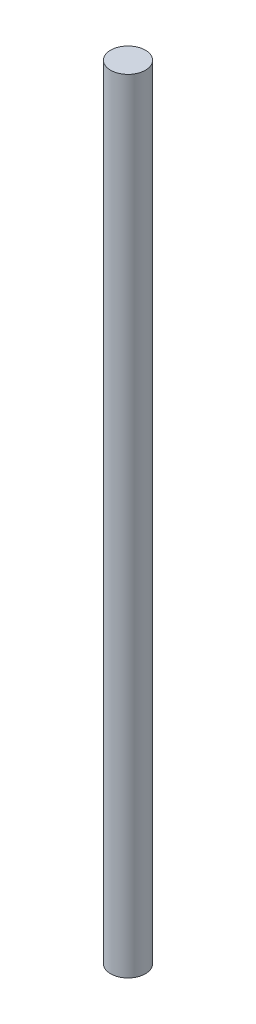
SolidWorks part; units mm, degrees
ref_plane "Front Plane" through (0, 0, 0) normal (0, 0, 1) x (1, 0, 0)
ref_plane "Top Plane" through (0, 0, 0) normal (0, 1, 0) x (1, 0, 0)
ref_plane "Right Plane" through (0, 0, 0) normal (1, 0, 0) x (0, 0, -1)
sketch "Sketch1" plane through (0, 0, 0) normal (0, 1, 0) x (1, 0, 0)
  circle A0 centre (0, 0) radius 4
  dimension "D1" = 8
extrude "Boss-Extrude1" add sketch "Sketch1" along normal blind 180
